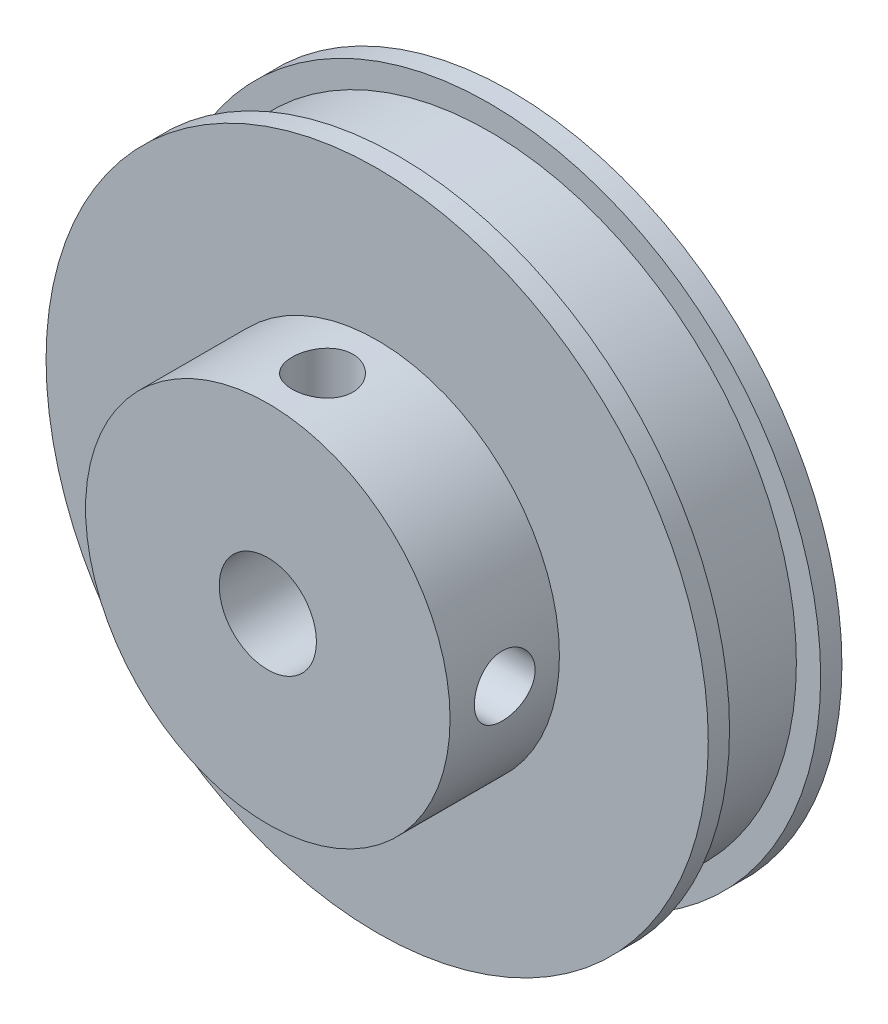
SolidWorks part; units mm, degrees
ref_plane "Front Plane" through (0, 0, 0) normal (0, 0, 1) x (1, 0, 0)
ref_plane "Top Plane" through (0, 0, 0) normal (0, 1, 0) x (1, 0, 0)
ref_plane "Right Plane" through (0, 0, 0) normal (1, 0, 0) x (0, 0, -1)
sketch "Sketch1" plane through (0, 0, 0) normal (0, 0, 1) x (1, 0, 0)
  circle A0 centre (0, 0) radius 27.25
extrude "Boss-Extrude1" add sketch "Sketch1" along normal blind 1.75
sketch "Sketch2" plane through (0, 0, 1.75) normal (0, 0, 1) x (1, 0, 0)
  circle A0 centre (0, 0) radius 25.25
extrude "Boss-Extrude2" add sketch "Sketch2" along normal blind 7.5
sketch "Sketch3" plane through (0, 0, 9.25) normal (0, 0, 1) x (1, 0, 0)
  circle A0 centre (0, 0) radius 27.25
extrude "Boss-Extrude3" add sketch "Sketch3" along normal blind 1.75
sketch "Sketch4" plane through (0, 0, 11) normal (0, 0, 1) x (1, 0, 0)
  circle A0 centre (0, 0) radius 15
extrude "Boss-Extrude4" add sketch "Sketch4" along normal blind 9
sketch "Sketch6" plane through (0, 0, 20) normal (0, 0, 1) x (1, 0, 0)
  circle A0 centre (0, 0) radius 4
extrude "Cut-Extrude1" cut sketch "Sketch6" against normal up to surface (20 mm away) up to face at (27.25, 0, 0)
ref_axis "Axis1" through (0, 0, 0) along (0, 0, 1)
ref_plane "Plane1" through (0, 0, 0) normal (-1, 0, 0) x (0, 0, 1)
sketch "Sketch7" plane through (0, 0, 0) normal (-1, 0, 0) x (0, 0, 1)
  line L0 (20, 0) -> (15.5, 0) construction
  line L1 (20, -15) -> (20, 15) construction
  line L2 (0, 0) -> (20, 0) construction
  circle A0 centre (15.5, 0) radius 2.5
extrude "Cut-Extrude2" cut sketch "Sketch7" against normal up to surface (15 mm away) up to face at (15, 0, 20)
ref_plane "Plane2" through (0, 0, 0) normal (0, -1, 0) x (0, 0, 1)
sketch "Sketch8" plane through (0, 0, 0) normal (0, -1, 0) x (0, 0, 1)
  line L0 (20, 0) -> (15.5, 0) construction
  line L1 (20, -15) -> (20, 15) construction
  line L2 (11, 0) -> (-11, 0) construction
  circle A0 centre (15.5, 0) radius 2.5
extrude "Cut-Extrude3" cut sketch "Sketch8" against normal up to surface (15 mm away) up to face at (14.9904, 0.5362, 13.0582)
